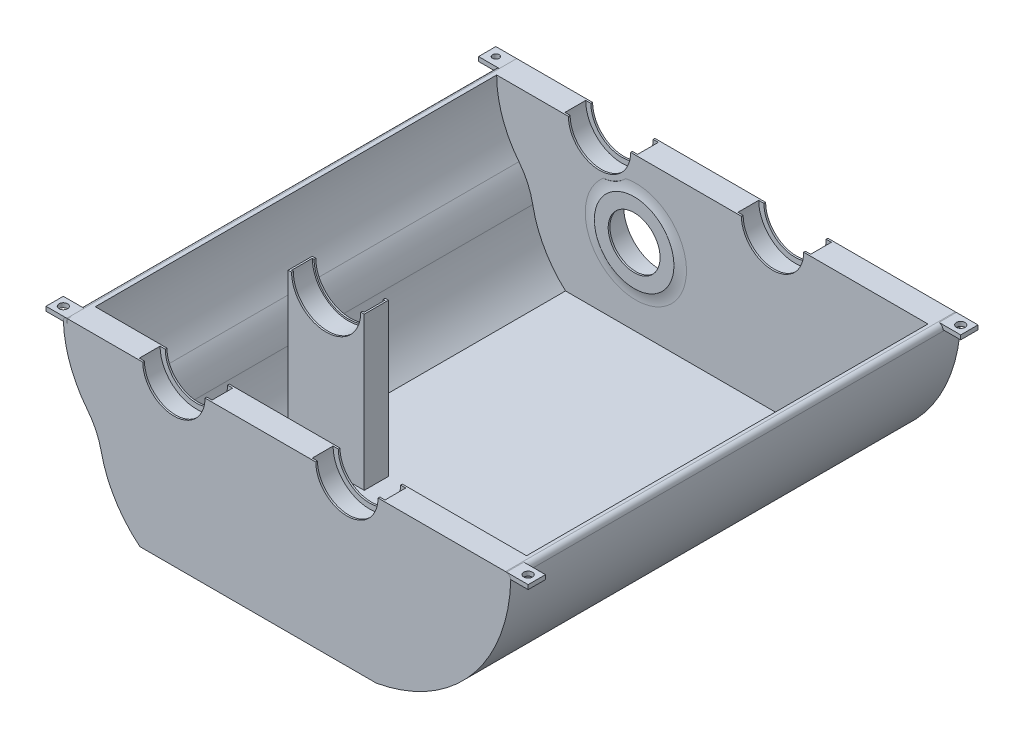
SolidWorks part; units mm, degrees
ref_plane "Front Plane" through (0, 0, 0) normal (0, 0, 1) x (1, 0, 0)
ref_plane "Top Plane" through (0, 0, 0) normal (0, 1, 0) x (1, 0, 0)
ref_plane "Right Plane" through (0, 0, 0) normal (1, 0, 0) x (0, 0, -1)
sketch "Sketch4" plane through (0, 0, 0) normal (0, 0, 1) x (1, 0, 0)
  line L0 (100, 33.0579) -> (100, -54.275)
  line L4 (0, -55.1421) -> (95.9941, -55.1421)
  line L6 (95.9941, -60.1421) -> (-40.6616, -60.1421)
  line L8 (-40.6616, -55.1421) -> (0, -55.1421)
  line L9 (-84.9276, 33.0579) -> (-80.4576, 33.0579)
  line L10 (168.8223, 33.0579) -> (173.7367, 33.0579)
  line L11 (-42, 33.0579) -> (-75.2773, 8.785)
  line L12 (0, 33.0579) -> (39.5, 11.4579)
  arc A3 (-40.6616, -55.1421) -> (-60.6393, -11.2584) centre (0, -10.1421) cw
  arc A4 (-40.6616, -60.1421) -> (-64.3346, -13.9405) centre (0, -10.1421) cw
  arc A5 (95.9941, -55.1421) -> (168.8223, 33.0579) centre (79, 33.0579) ccw
  arc A6 (95.9941, -60.1421) -> (173.7367, 33.0579) centre (79, 33.0579) ccw
  arc A7 (-60.6393, -11.2584) -> (-80.4576, 33.0579) centre (-21, 33.0579) cw
  arc A8 (-64.3346, -13.9405) -> (-84.9276, 33.0579) centre (-21, 33.0579) cw
  arc A9 (58, 33.0579) -> (100, 33.0579) centre (79, 33.0579) ccw
  circle A10 centre (0, -10.1421) radius 21
  arc A11 (-42, 33.0579) -> (0, 33.0579) centre (-21, 33.0579) ccw
extrude "Boss-Extrude2" add sketch "Sketch4" along normal blind 260 contours L4 A5 L10 A6 L6 A4 A8 L9 A7 A3 L8
sketch "Sketch5" plane through (0, 0, 0) normal (0, 0, -1) x (-1, 0, 0)
  line L0 (-100, 33.0579) -> (-168.8223, 33.0579)
  line L1 (42, 33.0579) -> (80.4576, 33.0579)
  line L2 (-95.9941, -55.1421) -> (40.6616, -55.1421)
  line L3 (0, 33.0579) -> (-58, 33.0579)
  arc A0 (-100, 33.0579) -> (-58, 33.0579) centre (-79, 33.0579) ccw
  arc A1 (-100, 33.0579) -> (-58, 33.0579) centre (-79, 33.0579) ccw construction
  arc A2 (-95.9941, -55.1421) -> (-168.8223, 33.0579) centre (-79, 33.0579) cw
  arc A3 (0, 33.0579) -> (42, 33.0579) centre (21, 33.0579) ccw
  arc A4 (40.6616, -55.1421) -> (60.6393, -11.2584) centre (0, -10.1421) ccw
  arc A5 (40.6616, -55.1421) -> (60.6393, -11.2584) centre (0, -10.1421) ccw construction
  arc A6 (60.6393, -11.2584) -> (75.4717, 9.2244) centre (21, 33.0579) ccw
  arc A7 (-168.8223, 33.0579) -> (-95.9941, -55.1421) centre (-79, 33.0579) ccw construction
  arc M1 (60.6393, -11.2584) -> (40.6616, -55.1421) centre (0, -10.1421) cw
  line M2 (40.6616, -55.1421) -> (-95.9941, -55.1421)
  arc M10 (80.4576, 33.0579) -> (60.6393, -11.2584) centre (21, 33.0579) cw
extrude "Boss-Extrude3" add sketch "Sketch5" against normal blind 14 contours A3 A0 M2 M1 M10 region at (44.7557, -10.1549, 0)
sketch "Sketch32" plane through (0, 33.0579, 0) normal (0, 1, 0) x (1, 0, 0)
  line L0 (173.7367, -260) -> (183.7367, -260)
  line L1 (183.7367, -260) -> (183.7367, -250)
  line L2 (183.7367, -250) -> (173.7367, -250)
  line L3 (173.7367, -260) -> (173.7367, 0) construction
  line L4 (183.7367, -255) -> (173.7367, -255) construction
  line L5 (173.7367, 0) -> (183.7367, 0)
  line L6 (183.7367, 0) -> (183.7367, -10)
  line L7 (183.7367, -10) -> (173.7367, -10)
  line L8 (183.7367, -5) -> (173.7367, -5) construction
  line L11 (173.7367, -10) -> (171.2367, -10)
  line L12 (171.2367, -10) -> (171.2367, 0)
  line L13 (-84.9276, 0) -> (-42, 0) construction
  line L14 (171.2367, 0) -> (173.7367, 0)
  line L15 (173.7367, -260) -> (171.2367, -260)
  line L16 (-84.9276, -260) -> (-80.4576, -260) construction
  line L17 (171.2367, -260) -> (171.2367, -250)
  line L18 (171.2367, -250) -> (173.7367, -250)
  line L19 (-84.9276, -260) -> (-94.9276, -260)
  line L20 (-94.9276, -260) -> (-94.9276, -250)
  line L21 (-94.9276, -250) -> (-84.9276, -250)
  line L22 (-84.9276, -260) -> (-84.9276, 0) construction
  line L23 (-94.9276, -255) -> (-84.9276, -255) construction
  line L24 (-84.9276, -250) -> (-82.4276, -250)
  line L25 (-82.4276, -250) -> (-82.4276, -260)
  line L26 (-84.9276, -260) -> (-80.4576, -260) construction
  line L27 (-82.4276, -260) -> (-84.9276, -260)
  line L28 (-84.9276, 0) -> (-94.9276, 0)
  line L29 (-94.9276, 0) -> (-94.9276, -10)
  line L30 (-94.9276, -10) -> (-84.9276, -10)
  line L31 (-84.9276, 0) -> (-82.4276, 0)
  line L32 (-84.9276, 0) -> (-42, 0) construction
  line L33 (-82.4276, 0) -> (-82.4276, -10)
  line L34 (-82.4276, -10) -> (-84.9276, -10)
  line L35 (-94.9276, -5) -> (-84.9276, -5) construction
  circle A0 centre (178.7367, -255) radius 2.5
  circle A1 centre (178.7367, -5) radius 2.5
  circle A2 centre (-89.9276, -255) radius 2.5
  circle A3 centre (-89.9276, -5) radius 1.8987
extrude "Boss-Extrude13" add sketch "Sketch32" against normal blind 2.5 separate body
sketch "Sketch6" plane through (0, 0, 0) normal (0, 0, -1) x (-1, 0, 0)
  circle A0 centre (0, -10.1421) radius 21.05
extrude "Cut-Extrude1" cut sketch "Sketch6" against normal through all
sketch "Sketch8" plane through (0, 0, 260) normal (0, 0, 1) x (1, 0, 0)
  line L6 (-40.4463, -56.4204) -> (95.9941, -55.1421)
  line L7 (-80.4576, 33.0579) -> (-42, 33.0579)
  line L8 (0, 33.0579) -> (58, 33.0579)
  line L9 (100, 33.0579) -> (168.8223, 33.0579)
  arc A5 (-42, 33.0579) -> (0, 33.0579) centre (-21, 33.0579) ccw
  arc A6 (58, 33.0579) -> (100, 33.0579) centre (79, 33.0579) ccw
  arc A7 (-80.4576, 33.0579) -> (-60.6393, -11.2584) centre (-21, 33.0579) ccw
  arc A8 (-60.6393, -11.2584) -> (-40.6616, -55.1421) centre (0, -10.1421) ccw construction
  arc A9 (-60.6393, -11.2584) -> (-40.4463, -56.4204) centre (0, -11.2407) ccw
  arc A10 (168.8223, 33.0579) -> (95.9941, -55.1421) centre (79, 33.0579) cw
  arc A11 (95.9941, -55.1421) -> (168.8223, 33.0579) centre (79, 33.0579) ccw construction
extrude "Boss-Extrude4" add sketch "Sketch8" against normal blind 14
sketch "Sketch9" plane through (0, -55.1421, 0) normal (0, 1, 0) x (1, 0, 0)
  line L0 (-21, -158) -> (1, -158)
  line L1 (-21, -172) -> (-21, -246) construction
  line L2 (-21, -14) -> (-21, -158) construction
  line L3 (-40.6616, -246) -> (95.9941, -246) construction
  line L4 (1, -158) -> (1, -172)
  line L5 (-42, -14) -> (0, -14) construction
  line L6 (1, -172) -> (-43, -172)
  line L7 (-43, -172) -> (-43, -158)
  line L8 (-43, -158) -> (-21, -158)
  line M2 (-40.6616, -14) -> (-40.6616, -246)
extrude "Boss-Extrude5" add sketch "Sketch9" along normal blind 88.2 contours L8 L6 L4 L0 M2 | L0 L4 L6 L7 L8 region at (-19.8308, -55.1421, 165)
sketch "Sketch16" plane through (0, 0, 172) normal (0, 0, 1) x (1, 0, 0)
  line L0 (1, 33.0579) -> (-43, 33.0579) construction
  circle A0 centre (-21, 33.0579) radius 21
extrude "Cut-Extrude4" cut sketch "Sketch16" against normal through all both
ref_plane "Plane12" through (0, 33.0579, 172) normal (0, 1, 0) x (1, 0, 0)
sketch "Sketch19" plane through (0, 33.0579, 172) normal (0, 1, 0) x (1, 0, 0)
  line L1 (1, 0) -> (1, 1)
  line L2 (1, 14) -> (1, 0) construction
  line L3 (1, 1) -> (-43, 1)
  line L4 (-43, 0) -> (-43, 14) construction
  line L5 (-43, 1) -> (-43, 0)
  line L6 (-43, 0) -> (1, 0)
extrude "Boss-Extrude9" add sketch "Sketch19" against normal blind 40
ref_plane "Plane13" through (0, 33.0579, 158) normal (0, -1, 0) x (-1, 0, 0)
sketch "Sketch21" plane through (0, 33.0579, 158) normal (0, -1, 0) x (-1, 0, 0)
  line L0 (0, 0) -> (42, 0)
  line L1 (42, 0) -> (42, -1)
  line L2 (42, 0) -> (42, -13) construction
  line L3 (42, -1) -> (0, -1)
  line L4 (0, -13) -> (0, 0) construction
  line L5 (0, -1) -> (0, 0)
extrude "Boss-Extrude10" add sketch "Sketch21" along normal blind 40
sketch "Sketch22" plane through (0, 0, 158) normal (0, 0, -1) x (-1, 0, 0)
  line L0 (43, 33.0579) -> (-1, 33.0579) construction
  circle A0 centre (21, 33.0579) radius 20
extrude "Cut-Extrude5" cut sketch "Sketch22" against normal through all both
fillet "Fillet7" radius 40 1 edges at (-60.6393, -11.2584, 130)
fillet "Fillet8" radius 40 1 edges at (-64.3346, -13.9405, 130)
sketch "Sketch26" plane through (0, 0, 14) normal (0, 0, 1) x (1, 0, 0)
  circle A0 centre (0, -10.1421) radius 23
  circle A1 centre (0, -10.1421) radius 15
  dimension "D1" = 46
  dimension "D2" = 30
extrude "Boss-Extrude11" add sketch "Sketch26" along normal blind 1 contours A0 | A1
fillet "Fillet9" radius 20 1 edges at (-23, -10.1421, 14)
sketch "Sketch27" plane through (0, 33.0579, 0) normal (0, 1, 0) x (1, 0, 0)
  line L0 (100, 0) -> (-42, 0)
  line L1 (-42, 0) -> (-42, -1)
  line L2 (-42, -14) -> (-42, 0) construction
  line L3 (-42, -1) -> (100, -1)
  line L4 (100, -14) -> (100, 0) construction
  line L5 (100, -1) -> (100, 0)
  line L6 (100, -246) -> (-42, -246)
  line L7 (100, -13) -> (-42, -13)
  line L8 (-42, -13) -> (-42, -14)
  line L9 (-42, -14) -> (100, -14)
  line L10 (100, -14) -> (100, -13)
  line L11 (-42, -246) -> (-42, -247)
  line L12 (-42, -246) -> (-42, -260) construction
  line L13 (-42, -247) -> (100, -247)
  line L14 (100, -246) -> (100, -260) construction
  line L15 (100, -247) -> (100, -246)
  line L17 (-42, -259) -> (100, -259)
  line L18 (100, -259) -> (100, -260)
  line L19 (100, -260) -> (-42, -260)
  line L20 (-42, -260) -> (-42, -259)
extrude "Boss-Extrude12" add sketch "Sketch27" against normal blind 25
sketch "Sketch28" plane through (0, 0, 260) normal (0, 0, 1) x (1, 0, 0)
  circle A0 centre (-21, 33.0579) radius 18
  circle A1 centre (79, 33.0579) radius 18
extrude "Cut-Extrude7" cut sketch "Sketch28" against normal through all both
sketch "Sketch31" plane through (0, 0, 0) normal (0, 0, -1) x (-1, 0, 0)
  circle A0 centre (0, -10.1421) radius 21.05
extrude "Cut-Extrude8" cut sketch "Sketch31" against normal blind 14
fillet "Fillet12" radius 2 1 edges at (-84.9276, 33.0579, 130)
fillet "Fillet15" radius 3 1 edges at (173.7367, 33.0579, 130)
